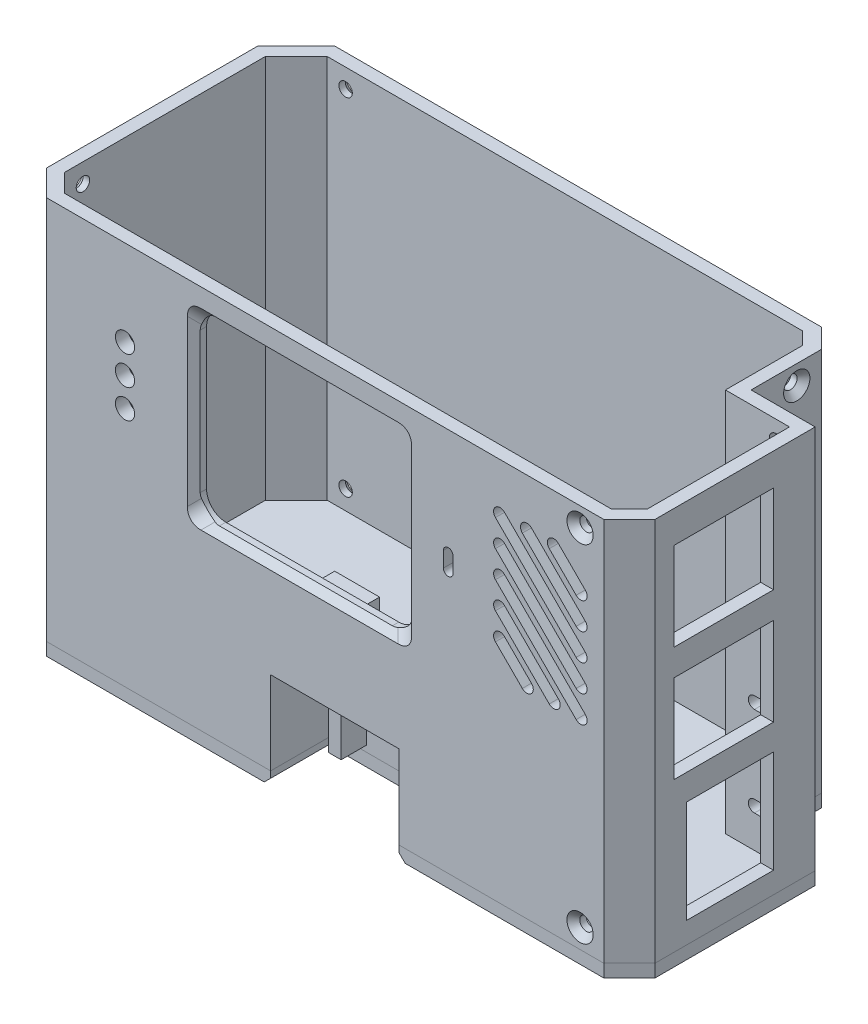
SolidWorks part; units mm, degrees
ref_plane "前视基准面" through (0, 0, 0) normal (0, 0, 1) x (1, 0, 0)
ref_plane "上视基准面" through (0, 0, 0) normal (0, 1, 0) x (1, 0, 0)
ref_plane "右视基准面" through (0, 0, 0) normal (1, 0, 0) x (0, 0, -1)
other "Configuration Table"
sketch "草图1" plane through (0, 0, 0) normal (0, 0, 1) x (1, 0, 0)
  line L1 (-105.5174, 35.9027) -> (-10.5174, 35.9027)
  line L2 (-105.5174, 35.9027) -> (-105.5174, -26.0973)
  line L3 (-105.5174, -26.0973) -> (-10.5174, -26.0973)
  line L4 (-10.5174, 35.9027) -> (-10.5174, -26.0973)
  dimension "D1" = 62
  dimension "D2" = 95
extrude "凸台-拉伸1" add sketch "草图1" along normal blind 43
sketch "草图4" plane through (0, -26.0973, 0) normal (0, -1, 0) x (1, 0, 0)
  line L0 (-10.5174, 43) -> (-10.5174, 0) construction
  line L1 (-10.5174, 14) -> (-20.5174, 14)
  line L2 (-10.5174, 14) -> (-10.5174, 0)
  line L3 (-10.5174, 0) -> (-20.5174, 0)
  line L4 (-20.5174, 14) -> (-20.5174, 0)
  line L5 (-105.5174, 0) -> (-10.5174, 0) construction
  dimension "D1" = 14
  dimension "D2" = 10
extrude "切除-拉伸3" cut sketch "草图4" against normal up to next
chamfer "倒角2" distance 6 angle 45 1 edges at (-105.5174, 4.9027, 0)
chamfer "倒角3" distance 4 angle 45 2 edges at (-105.5174, 4.9027, 43) (-10.5174, 4.9027, 43)
sketch "草图7" plane through (0, 0, 43) normal (0, 0, 1) x (1, 0, 0)
  line L0 (-101.5174, -26.0973) -> (-14.5174, -26.0973) construction
  line L1 (-46.5174, -26.0973) -> (-66.5174, -26.0973)
  line L2 (-46.5174, -26.0973) -> (-46.5174, -6.0973)
  line L3 (-46.5174, -6.0973) -> (-66.5174, -6.0973)
  line L4 (-66.5174, -26.0973) -> (-66.5174, -6.0973)
  line L6 (-10.5174, -26.0973) -> (-10.5174, 35.9027) construction
  dimension "D1" = 36
  dimension "D2" = 20
  dimension "D3" = 20
extrude "切除-拉伸5" cut sketch "草图7" against normal blind 10
shell "抽壳3" thickness 2 removed face at (-54.2952, 35.9027, 22)
sketch "草图9" plane through (0, -6.0973, 0) normal (0, -1, 0) x (1, 0, 0)
  line L0 (-44.5174, 41) -> (-68.5174, 41) construction
  line L1 (-46.5174, 41) -> (-66.5174, 41)
  line L2 (-46.5174, 41) -> (-46.5174, 33)
  line L3 (-46.5174, 33) -> (-66.5174, 33)
  line L4 (-66.5174, 41) -> (-66.5174, 33)
  line L5 (-66.5174, 33) -> (-46.5174, 33) construction
  line L8 (-66.5174, 33) -> (-66.5174, 43) construction
  line L9 (-46.5174, 33) -> (-46.5174, 43) construction
extrude "切除-拉伸6" cut sketch "草图9" against normal blind 10
sketch "草图10" plane through (0, -6.0973, 0) normal (0, -1, 0) x (1, 0, 0)
  line L4 (-66.5174, 43) -> (-66.5174, 41)
  line L5 (-66.5174, 41) -> (-46.5174, 41)
  line L6 (-46.5174, 41) -> (-46.5174, 43)
  line L7 (-46.5174, 43) -> (-66.5174, 43)
  line L8 (-66.5174, 43) -> (-66.5174, 41)
  line L9 (-66.5174, 41) -> (-46.5174, 41)
  line L10 (-46.5174, 41) -> (-46.5174, 43)
  line L11 (-46.5174, 43) -> (-66.5174, 43)
  dimension "D1" = 0
extrude "凸台-拉伸2" add sketch "草图10" along normal blind 5
sketch "草图11" plane through (0, 0, 43) normal (0, 0, 1) x (1, 0, 0)
  line L0 (-97.0174, 3.0227) -> (-76.0174, 3.0227) construction
  line L1 (-44.5121, 32.986) -> (-79.5174, 32.986)
  line L2 (-44.5121, 32.986) -> (-44.5121, 3.0227)
  line L3 (-44.5121, 3.0227) -> (-79.5174, 3.0227)
  line L4 (-79.5174, 32.986) -> (-79.5174, 3.0227)
  arc A0 (-44.0174, 32.8768) -> (-45.0174, 33.0227) centre (-45.0174, 29.5227) ccw construction
extrude "切除-拉伸7" cut sketch "草图11" against normal blind 1 draft 45
sketch "草图35" plane through (0, 0, 42) normal (0, 0, 1) x (1, 0, 0)
  line L4 (-45.5121, 4.0227) -> (-45.5121, 31.986)
  line L5 (-45.5121, 31.986) -> (-78.5174, 31.986)
  line L6 (-78.5174, 31.986) -> (-78.5174, 4.0227)
  line L7 (-78.5174, 4.0227) -> (-45.5121, 4.0227)
  line L8 (-45.5121, 4.0227) -> (-45.5121, 31.986)
  line L9 (-45.5121, 31.986) -> (-78.5174, 31.986)
  line L10 (-78.5174, 31.986) -> (-78.5174, 4.0227)
  line L11 (-78.5174, 4.0227) -> (-45.5121, 4.0227)
  dimension "D1" = 0
extrude "切除-拉伸27" cut sketch "草图35" against normal up to next
fillet "圆角1" radius 3 8 edges at (-79.0174, 32.486, 42.5) (-79.0174, 3.5227, 42.5) (-45.0121, 3.5227, 42.5) (-45.0121, 32.486, 42.5) (-45.5121, 4.0227, 41.5) (-78.5174, 4.0227, 41.5) (-45.5121, 31.986, 41.5) (-78.5174, 31.986, 41.5)
sketch "草图12" plane through (0, 0, 33) normal (0, 0, 1) x (1, 0, 0)
  line L0 (-46.5174, -4.0973) -> (-66.5174, -4.0973) construction
  line L1 (-63.5174, -4.0973) -> (-49.5174, -4.0973)
  line L2 (-63.5174, -4.0973) -> (-63.5174, -23.0973)
  line L3 (-63.5174, -23.0973) -> (-49.5174, -23.0973)
  line L4 (-49.5174, -4.0973) -> (-49.5174, -23.0973)
  line L5 (-66.5174, -4.0973) -> (-66.5174, -11.0973) construction
  line L6 (-46.5174, -4.0973) -> (-46.5174, -11.0973) construction
  line L7 (-66.5174, -26.0973) -> (-46.5174, -26.0973) construction
  dimension "D1" = 3
  dimension "D2" = 3
  dimension "D3" = 3
extrude "凸台-拉伸3" add sketch "草图12" along normal blind 4
sketch "草图13" plane through (0, -4.0973, 0) normal (0, 1, 0) x (1, 0, 0)
  line L0 (-44.5174, -31) -> (-68.5174, -31) construction
  line L1 (-61.5174, -31) -> (-51.5174, -31)
  line L2 (-61.5174, -31) -> (-61.5174, -35.5752)
  line L3 (-61.5174, -35.5752) -> (-51.5174, -35.5752)
  line L4 (-51.5174, -31) -> (-51.5174, -35.5752)
  line L5 (-68.5174, -31) -> (-68.5174, -41) construction
  line L6 (-44.5174, -31) -> (-44.5174, -41) construction
  dimension "D1" = 7
  dimension "D2" = 7
extrude "切除-拉伸8" cut sketch "草图13" against normal blind 17
sketch "草图14" plane through (0, 0, 37) normal (0, 0, 1) x (1, 0, 0)
  line L0 (-63.5174, -23.0973) -> (-49.5174, -23.0973) construction
  line L1 (-61.5174, -4.0973) -> (-51.5174, -4.0973)
  line L2 (-61.5174, -4.0973) -> (-61.5174, -23.0973)
  line L3 (-61.5174, -23.0973) -> (-51.5174, -23.0973)
  line L4 (-51.5174, -4.0973) -> (-51.5174, -23.0973)
extrude "切除-拉伸9" cut sketch "草图14" against normal up to surface (4 mm away) up to face at (-56.5174, -14.3473, 33)
chamfer "倒角4" distance 1 angle 45 2 edges at (-66.5174, -26.0973, 38) (-46.5174, -26.0973, 38)
sketch "草图15" plane through (-10.5174, 0, 0) normal (1, 0, 0) x (0, 0, -1)
  line L1 (-34.05, -4.7773) -> (-20.5, -4.7773)
  line L2 (-34.05, -4.7773) -> (-34.05, -20.7773)
  line L3 (-34.05, -20.7773) -> (-20.5, -20.7773)
  line L4 (-20.5, -4.7773) -> (-20.5, -20.7773)
  line L5 (-36, 13.0027) -> (-20.5, 13.0027)
  line L6 (-36, 13.0027) -> (-36, -0.7573)
  line L7 (-36, -0.7573) -> (-20.5, -0.7573)
  line L8 (-20.5, 13.0027) -> (-20.5, -0.7573)
  line L9 (-36, 30.9027) -> (-20.5, 30.9027)
  line L10 (-36, 30.9027) -> (-36, 17.1427)
  line L11 (-36, 17.1427) -> (-20.5, 17.1427)
  line L12 (-20.5, 30.9027) -> (-20.5, 17.1427)
extrude "切除-拉伸10" cut sketch "草图15" against normal blind 2
sketch "草图16" plane through (0, 0, 43) normal (0, 0, 1) x (1, 0, 0)
  line L0 (-38.7974, 19.2043) -> (-38.7974, 16.8043) construction
  line L1 (-38.0444, 19.2043) -> (-38.0444, 16.8043)
  line L2 (-39.5504, 19.2043) -> (-39.5504, 16.8043)
  line L3 (-46.5121, 28.8647) -> (-46.5121, 7.144) construction
  line L5 (-44.5121, 18.0043) -> (-51.3378, 18.0043) construction
  line L6 (-10.5174, -26.0973) -> (-10.5174, 35.9027) construction
  arc A0 (-38.0444, 19.2043) -> (-39.5504, 19.2043) centre (-38.7974, 19.2043) ccw
  arc A1 (-39.5504, 16.8043) -> (-38.0444, 16.8043) centre (-38.7974, 16.8043) ccw
  point P2 (-38.7974, 18.0043)
  point P14 (-46.5121, 18.0043)
  dimension "D1" = 2.4
  dimension "D2" = 28.28
extrude "切除-拉伸11" cut sketch "草图16" against normal blind 2
sketch "草图17" plane through (0, -26.0973, 0) normal (0, -1, 0) x (1, 0, 0)
  line L0 (-105.5174, 39) -> (-105.5174, 6) construction
  line L1 (-93.9174, 13.067) -> (-84.4174, 13.067)
  line L2 (-93.9174, 13.067) -> (-93.9174, 16.567)
  line L3 (-93.9174, 16.567) -> (-84.4174, 16.567)
  line L4 (-84.4174, 13.067) -> (-84.4174, 16.567)
  line L6 (-93.9174, 20.3114) -> (-84.4174, 20.3114)
  line L7 (-93.9174, 20.3114) -> (-93.9174, 23.8114)
  line L8 (-93.9174, 23.8114) -> (-84.4174, 23.8114)
  line L9 (-84.4174, 20.3114) -> (-84.4174, 23.8114)
  line L10 (-78.1448, 23.5342) -> (-71.5448, 23.5342)
  line L11 (-78.1448, 23.5342) -> (-78.1448, 20.3114)
  line L12 (-78.1448, 20.3114) -> (-71.5448, 20.3114)
  line L13 (-71.5448, 23.5342) -> (-71.5448, 20.3114)
  line L14 (-64.6448, 23.6466) -> (-58.0448, 23.6466)
  line L15 (-64.6448, 23.6466) -> (-64.6448, 20.3114)
  line L16 (-64.6448, 20.3114) -> (-58.0448, 20.3114)
  line L17 (-58.0448, 23.6466) -> (-58.0448, 20.3114)
  line L19 (-83.4263, 17.1002) -> (-76.4263, 17.1002)
  line L20 (-83.4263, 17.1002) -> (-83.4263, 13.067)
  line L21 (-83.4263, 13.067) -> (-76.4263, 13.067)
  line L22 (-76.4263, 17.1002) -> (-76.4263, 13.067)
  line L23 (-74.9763, 17.1002) -> (-67.9763, 17.1002)
  line L24 (-74.9763, 17.1002) -> (-74.9763, 13.067)
  line L25 (-74.9763, 13.067) -> (-67.9763, 13.067)
  line L26 (-67.9763, 17.1002) -> (-67.9763, 13.067)
  line L27 (-51.5174, 16.567) -> (-43.9374, 16.567)
  line L28 (-51.5174, 16.567) -> (-51.5174, 13.767)
  line L29 (-51.5174, 13.767) -> (-43.9374, 13.767)
  line L30 (-43.9374, 16.567) -> (-43.9374, 13.767)
  line L31 (-63.5659, 16.567) -> (-52.9233, 16.567)
  line L32 (-63.5659, 16.567) -> (-63.5659, 14.767)
  line L33 (-63.5659, 14.767) -> (-52.9233, 14.767)
  line L34 (-52.9233, 16.567) -> (-52.9233, 14.767)
  dimension "D1" = 11.6
  dimension "D2" = 27.3726
  dimension "D3" = 6.9
  dimension "D4" = 6.6
  dimension "D5" = 7
  dimension "D6" = 1.45
  dimension "D7" = 9.5
  dimension "D8" = 3.5
  dimension "D9" = 2.8
  dimension "D10" = 54
  dimension "D11" = 7.58
  dimension "D12" = 1.4059
  dimension "D13" = 1.8
extrude "切除-拉伸12" cut sketch "草图17" against normal blind 2
chamfer "倒角9" distance 1 angle 45 12 edges at (-78.1448, -24.0973, 21.9228) (-74.8448, -24.0973, 23.5342) (-71.5448, -24.0973, 21.9228) (-74.8448, -24.0973, 20.3114) (-61.3448, -24.0973, 23.6466) (-64.6448, -24.0973, 21.979) (-58.0448, -24.0973, 21.979) (-61.3448, -24.0973, 20.3114) (-51.5174, -24.0973, 15.167) (-47.7274, -24.0973, 16.567) (-43.9374, -24.0973, 15.167) (-47.7274, -24.0973, 13.767)
fillet "圆角2" radius 1.2 8 edges at (-93.9174, -25.0973, 16.567) (-84.4174, -25.0973, 16.567) (-84.4174, -25.0973, 13.067) (-93.9174, -25.0973, 13.067) (-93.9174, -25.0973, 20.3114) (-93.9174, -25.0973, 23.8114) (-84.4174, -25.0973, 23.8114) (-84.4174, -25.0973, 20.3114)
fillet "圆角3" radius 0.5 18 edges at (-43.9374, -25.5973, 13.767) (-51.5174, -25.5973, 13.767) (-64.6448, -25.5973, 23.6466) (-58.0448, -25.5973, 23.6466) (-71.5448, -25.5973, 23.5342) (-78.1448, -25.5973, 23.5342) (-67.9763, -25.0973, 17.1002) (-74.9763, -25.0973, 17.1002) (-76.4263, -25.0973, 17.1002) (-83.4263, -25.0973, 17.1002) (-83.4263, -25.0973, 13.067) (-74.9763, -25.0973, 13.067) (-76.4263, -25.0973, 13.067) (-67.9763, -25.0973, 13.067) (-63.5659, -25.0973, 14.767) (-63.5659, -25.0973, 16.567) (-52.9233, -25.0973, 16.567) (-52.9233, -25.0973, 14.767)
chamfer "倒角7" distance 1 angle 45 6 edges at (-51.5174, -25.5973, 16.567) (-43.9374, -25.5973, 16.567) (-58.0448, -25.5973, 20.3114) (-64.6448, -25.5973, 20.3114) (-78.1448, -25.5973, 20.3114) (-71.5448, -25.5973, 20.3114)
sketch "草图18" plane through (0, 0, 43) normal (0, 0, 1) x (1, 0, 0)
  line L1 (-79.5174, 18.0043) -> (-81.9758, 18.0043) construction
  circle A0 centre (-89.2561, 13.5043) radius 1.5
  circle A1 centre (-89.2561, 18.0043) radius 1.5
  circle A2 centre (-89.2561, 22.5043) radius 1.5
  dimension "D3" = 3
  dimension "D2" = 3
extrude "切除-拉伸13" cut sketch "草图18" against normal blind 2
sketch "草图20" plane through (0, -24.0973, 0) normal (0, 1, 0) x (1, 0, 0)
  line L1 (-83.4263, -13.567) -> (-76.9263, -13.567)
  line L2 (-83.4263, -13.567) -> (-83.4263, -16.6002)
  line L3 (-83.4263, -16.6002) -> (-76.9263, -16.6002)
  line L4 (-76.9263, -13.567) -> (-76.9263, -16.6002)
  line L5 (-74.9763, -13.567) -> (-68.4763, -13.567)
  line L6 (-74.9763, -13.567) -> (-74.9763, -16.6002)
  line L7 (-74.9763, -16.6002) -> (-68.4763, -16.6002)
  line L8 (-68.4763, -13.567) -> (-68.4763, -16.6002)
extrude "凸台-拉伸4" add sketch "草图20" against normal blind 1
sketch "草图21" plane through (0, -25.0973, 0) normal (0, -1, 0) x (1, 0, 0)
  line L0 (-76.9263, 13.567) -> (-83.4263, 13.567) construction
  line L1 (-76.9263, 16.6002) -> (-80.9263, 16.6002)
  line L2 (-76.9263, 16.6002) -> (-76.9263, 13.567)
  line L3 (-76.9263, 13.567) -> (-80.9263, 13.567)
  line L4 (-80.9263, 16.6002) -> (-80.9263, 13.567)
  line L5 (-68.4763, 13.567) -> (-74.9763, 13.567) construction
  line L6 (-68.4763, 16.6002) -> (-72.4763, 16.6002)
  line L7 (-68.4763, 16.6002) -> (-68.4763, 13.567)
  line L8 (-68.4763, 13.567) -> (-72.4763, 13.567)
  line L9 (-72.4763, 16.6002) -> (-72.4763, 13.567)
  dimension "D1" = 4
extrude "凸台-拉伸5" add sketch "草图21" along normal up to surface (1 mm away) up to face at (-61.3448, -26.0973, 22.1299)
fillet "圆角4" radius 0.5 10 edges at (-74.9763, -25.0973, 15.0836) (-83.4263, -25.0973, 15.0836) (-80.9263, -25.5973, 13.567) (-80.9263, -25.5973, 16.6002) (-72.4763, -25.5973, 16.6002) (-72.4763, -25.5973, 13.567) (-68.4763, -25.0973, 16.6002) (-68.4763, -25.0973, 13.567) (-76.9263, -25.0973, 13.567) (-76.9263, -25.0973, 16.6002)
chamfer "倒角10" distance 2 angle 45 1 edges at (-22.5174, 5.9027, 2)
chamfer "倒角11" distance 3 angle 45 1 edges at (-20.5174, 4.9027, 0)
sketch "草图26" plane through (-20.5174, 0, 0) normal (1, 0, 0) x (0, 0, -1)
  line L0 (-10, 18.9027) -> (-10, -21.0973) construction
  line L1 (-8.6566, 18.9027) -> (-8.6566, -21.0973)
  line L2 (-11.3434, 18.9027) -> (-11.3434, -21.0973)
  line L3 (-14, -26.0973) -> (-3, -26.0973) construction
  line L5 (0, 35.9027) -> (0, -26.0973) construction
  arc A0 (-8.6566, 18.9027) -> (-11.3434, 18.9027) centre (-10, 18.9027) ccw
  arc A1 (-11.3434, -21.0973) -> (-8.6566, -21.0973) centre (-10, -21.0973) ccw
  point P2 (-10, -1.0973)
  dimension "D1" = 40
  dimension "D2" = 25
  dimension "D3" = 10
extrude "切除-拉伸15" cut sketch "草图26" against normal up to next
sketch "草图27" plane through (0, 0, 43) normal (0, 0, 1) x (1, 0, 0)
  line L0 (-10.5174, 35.9027) -> (-10.5174, -26.0973) construction
  line L2 (-22.3174, 28.4027) -> (-18.1174, 24.2027) construction
  line L3 (-21.6103, 29.1098) -> (-17.4103, 24.9098)
  line L4 (-23.0245, 27.6956) -> (-18.8245, 23.4956)
  line L5 (-26.5174, 28.4027) -> (-18.1174, 20.0027) construction
  line L6 (-25.8103, 29.1098) -> (-17.4103, 20.7098)
  line L7 (-27.2245, 27.6956) -> (-18.8245, 19.2956)
  line L8 (-30.7174, 28.4027) -> (-18.1174, 15.8027) construction
  line L9 (-30.0103, 29.1098) -> (-17.4103, 16.5098)
  line L10 (-31.4245, 27.6956) -> (-18.8245, 15.0956)
  line L11 (-30.7174, 24.2027) -> (-18.1174, 11.6027) construction
  line L12 (-30.0103, 24.9098) -> (-17.4103, 12.3098)
  line L13 (-31.4245, 23.4956) -> (-18.8245, 10.8956)
  line L14 (-30.7174, 20.0027) -> (-18.1174, 7.4027) construction
  line L15 (-30.0103, 20.7098) -> (-17.4103, 8.1098)
  line L16 (-31.4245, 19.2956) -> (-18.8245, 6.6956)
  line L17 (-22.3174, 7.4027) -> (-30.7174, 15.8027) construction
  line L18 (-23.0245, 6.6956) -> (-31.4245, 15.0956)
  line L19 (-21.6103, 8.1098) -> (-30.0103, 16.5098)
  line L20 (-30.7174, 11.6027) -> (-26.5174, 7.4027) construction
  line L21 (-30.0103, 12.3098) -> (-25.8103, 8.1098)
  line L22 (-31.4245, 10.8956) -> (-27.2245, 6.6956)
  line L23 (-14.5174, 35.9027) -> (-101.5174, 35.9027) construction
  circle A0 centre (-18.1174, 28.4027) radius 1 construction
  circle A1 centre (-22.3174, 28.4027) radius 1 construction
  circle A2 centre (-26.5174, 28.4027) radius 1 construction
  circle A3 centre (-30.7174, 28.4027) radius 1 construction
  circle A6 centre (-30.7174, 24.2027) radius 1 construction
  circle A9 centre (-30.7174, 20.0027) radius 1 construction
  circle A12 centre (-30.7174, 15.8027) radius 1 construction
  circle A15 centre (-30.7174, 11.6027) radius 1 construction
  circle A16 centre (-22.3174, 7.4027) radius 1 construction
  circle A17 centre (-26.5174, 7.4027) radius 1 construction
  circle A18 centre (-30.7174, 7.4027) radius 1 construction
  circle A25 centre (-18.1174, 24.2027) radius 1 construction
  circle A26 centre (-18.1174, 20.0027) radius 1 construction
  circle A27 centre (-18.1174, 15.8027) radius 1 construction
  circle A28 centre (-18.1174, 11.6027) radius 1 construction
  circle A29 centre (-18.1174, 7.4027) radius 1 construction
  circle A31 centre (-22.3174, 24.2027) radius 1 [skipped]
  circle A32 centre (-26.5174, 24.2027) radius 1 [skipped]
  circle A33 centre (-22.3174, 20.0027) radius 1 [skipped]
  circle A34 centre (-26.5174, 20.0027) radius 1 [skipped]
  circle A35 centre (-22.3174, 15.8027) radius 1 [skipped]
  circle A36 centre (-26.5174, 15.8027) radius 1 [skipped]
  circle A37 centre (-22.3174, 11.6027) radius 1 [skipped]
  circle A38 centre (-26.5174, 11.6027) radius 1 [skipped]
  arc A39 (-21.6103, 29.1098) -> (-23.0245, 27.6956) centre (-22.3174, 28.4027) ccw
  arc A40 (-18.8245, 23.4956) -> (-17.4103, 24.9098) centre (-18.1174, 24.2027) ccw
  arc A41 (-25.8103, 29.1098) -> (-27.2245, 27.6956) centre (-26.5174, 28.4027) ccw
  arc A42 (-18.8245, 19.2956) -> (-17.4103, 20.7098) centre (-18.1174, 20.0027) ccw
  arc A43 (-30.0103, 29.1098) -> (-31.4245, 27.6956) centre (-30.7174, 28.4027) ccw
  arc A44 (-18.8245, 15.0956) -> (-17.4103, 16.5098) centre (-18.1174, 15.8027) ccw
  arc A45 (-30.0103, 24.9098) -> (-31.4245, 23.4956) centre (-30.7174, 24.2027) ccw
  arc A46 (-18.8245, 10.8956) -> (-17.4103, 12.3098) centre (-18.1174, 11.6027) ccw
  arc A47 (-30.0103, 20.7098) -> (-31.4245, 19.2956) centre (-30.7174, 20.0027) ccw
  arc A48 (-18.8245, 6.6956) -> (-17.4103, 8.1098) centre (-18.1174, 7.4027) ccw
  arc A49 (-23.0245, 6.6956) -> (-21.6103, 8.1098) centre (-22.3174, 7.4027) ccw
  arc A50 (-30.0103, 16.5098) -> (-31.4245, 15.0956) centre (-30.7174, 15.8027) ccw
  arc A51 (-30.0103, 12.3098) -> (-31.4245, 10.8956) centre (-30.7174, 11.6027) ccw
  arc A52 (-27.2245, 6.6956) -> (-25.8103, 8.1098) centre (-26.5174, 7.4027) ccw
  point P4 (-20.2174, 26.3027)
  point P17 (-22.3174, 24.2027)
  point P24 (-24.4174, 22.1027)
  point P33 (-24.4174, 17.9027)
  point P46 (-24.4174, 13.7027)
  point P51 (-26.5174, 11.6027)
  point P56 (-28.6174, 9.5027)
  dimension "D3" = 2
  dimension "D1" = 7.6
  dimension "D2" = 7.5
  dimension "D4" = 4
  dimension "D5" = 6
sketch "草图29" plane through (-105.5174, 0, 0) normal (-1, 0, 0) x (0, 0, 1)
  line L0 (39, -26.0973) -> (6, -26.0973) construction
  circle A0 centre (35.3017, 32.9027) radius 1.05
  circle A1 centre (35.3017, -21.0973) radius 1.2021
  dimension "D1" = 2.1
  dimension "D2" = 5
extrude "切除-拉伸18" cut sketch "草图29" against normal up to next
sketch "草图30" plane through (0, 0, 0) normal (0, 0, -1) x (-1, 0, 0)
  line L0 (99.5174, -26.0973) -> (23.5174, -26.0973) construction
  circle A0 centre (95.8191, 32.9027) radius 1.05
  circle A1 centre (95.8191, -21.0973) radius 1.05
  dimension "D1" = 2.1
  dimension "D2" = 5
extrude "切除-拉伸19" cut sketch "草图30" against normal up to next
sketch "草图31" plane through (-20.5174, 0, 0) normal (1, 0, 0) x (0, 0, -1)
  line L0 (-14, -26.0973) -> (-3, -26.0973) construction
  circle A0 centre (-6.8698, 32.9027) radius 1.05
  circle A1 centre (-6.8698, -21.0973) radius 1.05
  dimension "D1" = 2.1
  dimension "D2" = 5
extrude "切除-拉伸20" cut sketch "草图31" against normal up to next
sketch "草图32" plane through (0, 0, 14) normal (0, 0, -1) x (-1, 0, 0)
  line L0 (10.5174, -26.0973) -> (20.5174, -26.0973) construction
  circle A0 centre (14.6174, 32.9027) radius 1.05
  circle A1 centre (14.6174, -21.0973) radius 1.05
  dimension "D1" = 2.1
  dimension "D2" = 5
extrude "切除-拉伸21" cut sketch "草图32" against normal up to next
sketch "草图33" plane through (0, 0, 43) normal (0, 0, 1) x (1, 0, 0)
  line L1 (-45.5174, -26.0973) -> (-14.5174, -26.0973) construction
  circle A0 centre (-18.2157, 32.9027) radius 1.05
  circle A1 centre (-18.2157, -21.0973) radius 1.05
  dimension "D1" = 2.1
  dimension "D2" = 5
extrude "切除-拉伸22" cut sketch "草图33" against normal up to next
chamfer "倒角20" distance 1 angle 45 10 edges at (-96.8691, 32.9027, 0) (-105.5174, 31.8527, 35.3017) (-17.1657, 32.9027, 43) (-15.6674, 32.9027, 14) (-20.5174, 32.9027, 5.8198) (-17.1657, -21.0973, 43) (-15.6674, -21.0973, 14) (-96.8691, -21.0973, 0) (-105.5174, -22.2995, 35.3017) (-20.5174, -21.0973, 5.8198)
sketch "草图34" plane through (0, 0, 14) normal (0, 0, -1) x (-1, 0, 0)
  line L0 (18.0174, -4.0973) -> (14.0174, -4.0973) construction
  line L1 (18.0174, -5.0973) -> (14.0174, -5.0973)
  line L2 (18.0174, -3.0973) -> (14.0174, -3.0973)
  line L3 (18.0174, -18.0973) -> (14.0174, -18.0973) construction
  line L4 (18.0174, -19.0973) -> (14.0174, -19.0973)
  line L5 (18.0174, -17.0973) -> (14.0174, -17.0973)
  line L7 (20.5174, 35.9027) -> (20.5174, -26.0973) construction
  arc A0 (18.0174, -5.0973) -> (18.0174, -3.0973) centre (18.0174, -4.0973) ccw
  arc A1 (14.0174, -3.0973) -> (14.0174, -5.0973) centre (14.0174, -4.0973) ccw
  arc A2 (18.0174, -19.0973) -> (18.0174, -17.0973) centre (18.0174, -18.0973) ccw
  arc A3 (14.0174, -17.0973) -> (14.0174, -19.0973) centre (14.0174, -18.0973) ccw
  point P3 (16.0174, -4.0973)
  point P8 (16.0174, -18.0973)
  dimension "D1" = 1
  dimension "D2" = 4
  dimension "D3" = 2.5
  dimension "D4" = 14
extrude "切除-拉伸25" cut sketch "草图34" against normal up to next (2 mm away) draft 2
extrude "切除-拉伸26" cut sketch "草图27" against normal up to next
split "分割1" bodies to split 138 resulting bodies 139 140 split by face at (-47.7274, -24.0973, 15.167)
